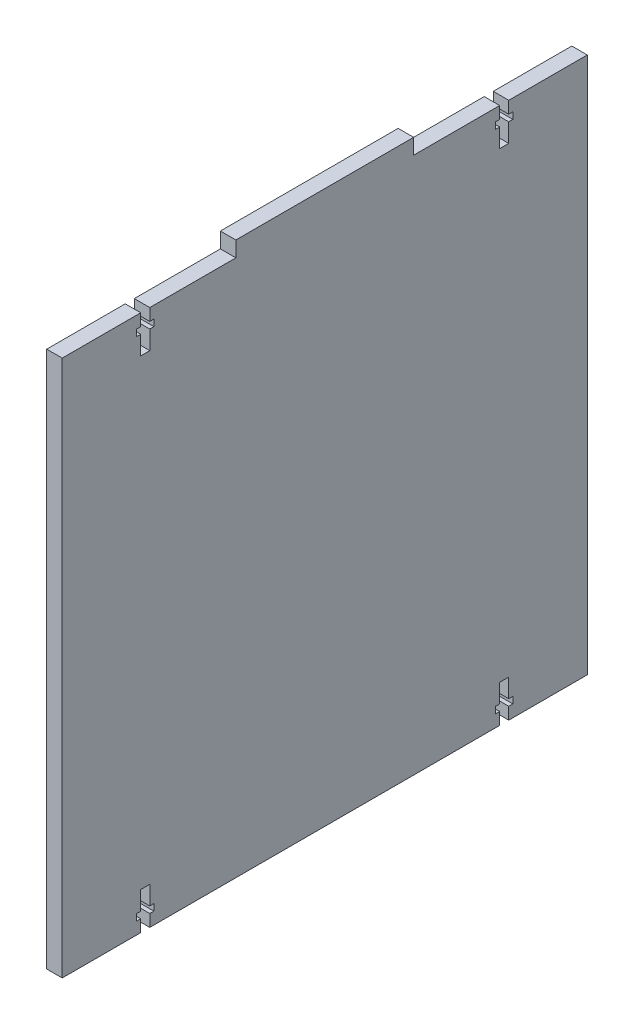
SolidWorks part; units mm, degrees
ref_plane "Front Plane" through (0, 0, 0) normal (0, 0, 1) x (1, 0, 0)
ref_plane "Top Plane" through (0, 0, 0) normal (0, 1, 0) x (1, 0, 0)
ref_plane "Right Plane" through (0, 0, 0) normal (1, 0, 0) x (0, 0, -1)
sketch "Sketch1" plane through (0, 0, 0) normal (1, 0, 0) x (0, 0, -1)
  line L1 (-35.6928, 37.9569) -> (138.1972, 37.9569)
  line L2 (-35.6928, 37.9569) -> (-35.6928, -139.8431)
  line L3 (-35.6928, -139.8431) -> (138.1972, -139.8431)
  line L4 (138.1972, 37.9569) -> (138.1972, -139.8431)
  dimension "D1" = 173.89
  dimension "D2" = 177.8
extrude "Main" add sketch "Sketch1" along normal blind 5.13
sketch "Sketch2" plane through (5.13, 0, 0) normal (1, 0, 0) x (0, 0, -1)
  line L0 (-9.6878, 37.9569) -> (-6.6908, 37.9569)
  line L1 (138.1972, 37.9569) -> (-35.6928, 37.9569) construction
  line L2 (-6.6908, 37.9569) -> (-6.6908, 33.9619)
  line L3 (-6.6908, 33.9619) -> (-5.3318, 33.9619)
  line L4 (-5.3318, 33.9619) -> (-5.3318, 31.7949)
  line L5 (-5.3318, 31.7949) -> (-6.6908, 31.7949)
  line L6 (-6.6908, 31.7949) -> (-6.6908, 25.5879)
  line L7 (-6.6908, 25.5879) -> (-9.6878, 25.5879)
  line L8 (-9.6878, 25.5879) -> (-9.6878, 31.7949)
  line L9 (-9.6878, 31.7949) -> (-11.0468, 31.7949)
  line L10 (-11.0468, 31.7949) -> (-11.0468, 33.9619)
  line L11 (-11.0468, 33.9619) -> (-9.6878, 33.9619)
  line L12 (-9.6878, 33.9619) -> (-9.6878, 37.9569)
  line L25 (-35.6928, -50.9431) -> (138.1972, -50.9431) construction
  line L26 (-35.6928, 37.9569) -> (-35.6928, -139.8431) construction
  line L27 (138.1972, -139.8431) -> (138.1972, 37.9569) construction
  dimension "D1" = 2.167
  dimension "D2" = 2.997
  dimension "D3" = 2.997
  dimension "D4" = 3.995
  dimension "D5" = 3.995
  dimension "D6" = 1.359
  dimension "D7" = 1.359
  dimension "D8" = 6.207
  dimension "D9" = 6.207
  dimension "D10" = 1.359
  dimension "D12" = 26.005
extrude "t-slot" cut sketch "Sketch2" against normal blind 5.13
ref_axis "Axis1" through (0, -50.9431, 35.6928) along (0, 0, -1)
pattern_linear "LPattern2" count 2 spacing 118.88 along (0, 0, -1) of "t-slot"
ref_plane "Plane1" through (0, -50.9431, 0) normal (0, -1, 0) x (1, 0, 0)
mirror "Mirror1" about plane through (0, -50.9431, 0) normal (0, -1, 0) of "LPattern2", "t-slot"
ref_axis "Axis2" through (5.13, 37.9569, -51.7457) along (-0.0288, -0.9996, 0)
sketch "Sketch6" plane through (0, 37.9569, 0) normal (0, 1, 0) x (1, 0, 0)
  line L0 (0, 109.1922) -> (0, -6.6908) construction
  line L1 (0, 80.6922) -> (5.13, 80.6922)
  line L2 (0, 80.6922) -> (0, 21.8122)
  line L3 (0, 21.8122) -> (5.13, 21.8122)
  line L4 (5.13, 80.6922) -> (5.13, 21.8122)
  line L5 (5.13, 109.1922) -> (5.13, -6.6908) construction
  line L6 (5.13, -35.6928) -> (0, -35.6928) construction
  point P8 (5.13, 51.2522)
  dimension "D1" = 86.945
  dimension "D2" = 58.88
extrude "Tooth" add sketch "Sketch6" along normal blind 5.13
equation "\"D1@Sketch6\" = \"D1@Sketch1\"/2"
